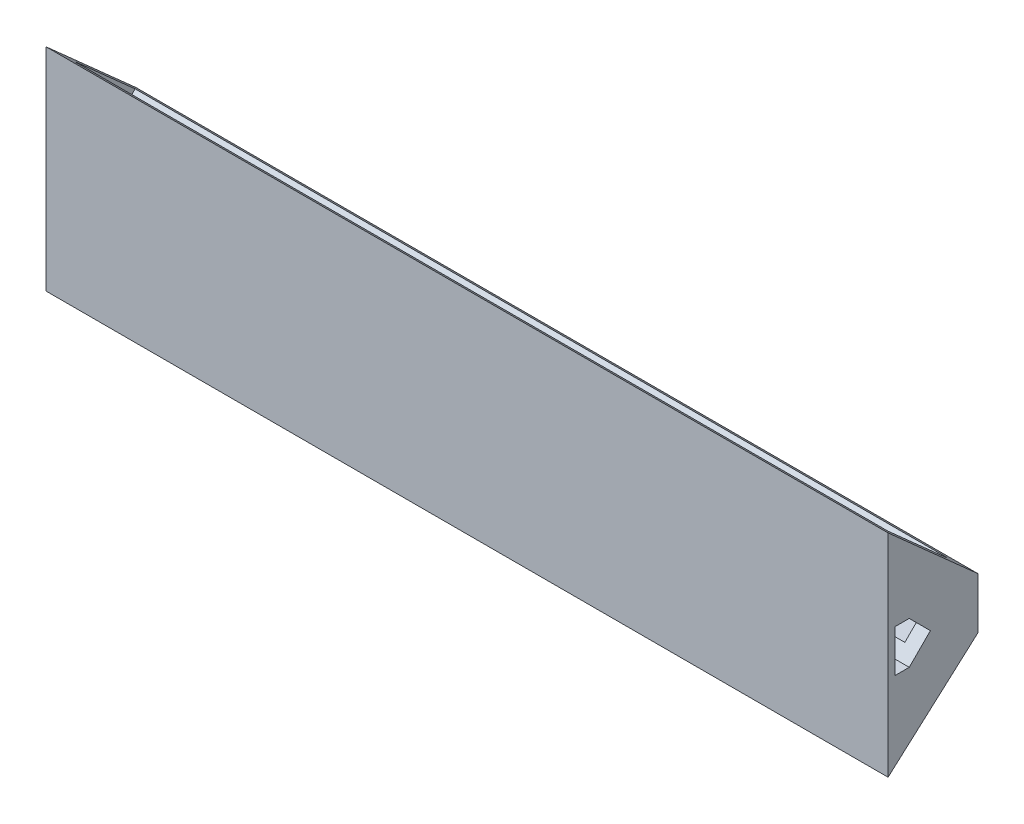
SolidWorks part; units mm, degrees
ref_plane "Front Plane" through (0, 0, 0) normal (0, 0, 1) x (1, 0, 0)
ref_plane "Top Plane" through (0, 0, 0) normal (0, 1, 0) x (1, 0, 0)
ref_plane "Right Plane" through (0, 0, 0) normal (1, 0, 0) x (0, 0, -1)
sketch "Sketch1" plane through (0, 0, 0) normal (0, 0, 1) x (1, 0, 0)
  line L0 (-115.4, 3.25) -> (115.4, -3.25) construction
  line L1 (-115.4, 3.25) -> (115.4, 3.25)
  line L2 (-115.4, 3.25) -> (-115.4, -3.25)
  line L3 (-115.4, -3.25) -> (115.4, -3.25)
  line L4 (115.4, 3.25) -> (115.4, -3.25)
  line L5 (-119.4, 7.25) -> (-119.4, -7.25)
  line L6 (-119.4, -7.25) -> (119.4, -7.25)
  line L7 (119.4, 7.25) -> (119.4, -7.25)
  line L8 (-119.4, 7.25) -> (119.4, 7.25)
  point P9 (0, 0)
  point P10 (0, 0)
  dimension "D1" = 6.5
  dimension "D2" = 230.8
  dimension "D3" = 4
sketch "Sketch4" plane through (0, 0, 0) normal (1, 0, 0) x (0, 0, -1)
  line L0 (-20, 8.7261) -> (-20, -2.0023) construction
  line L1 (0, 7.25) -> (0, -7.25) construction
  line L2 (0, 7.25) -> (-25.5, 30)
  line L3 (-25.5, 30) -> (-25.5, -30)
  line L4 (-25.5, 0) -> (0, 0) construction
  line L5 (-23.5, 6) -> (-23.5, -6)
  line L6 (-23.5, 6) -> (-19.5, 6)
  line L7 (-19.5, 6) -> (-13.5, 0)
  line L8 (-20.5, 4.0321) -> (-20.5, -1.7233) construction
  line L9 (0, -7.25) -> (-25.5, -30)
  line L10 (-19.5, -6) -> (-13.5, 0)
  line L11 (-23.5, -6) -> (-19.5, -6)
  line L12 (0, 7.25) -> (0, -7.25)
  point P9 (0, 0)
  point P12 (-25.5, -30)
  point P13 (-25.5, 30)
  point P14 (0, 5.6555)
  point P15 (0, 0)
  point P22 (-23.5, 0)
  point P23 (0, 0)
  dimension "D1" = 20
  dimension "D2" = 3
  dimension "D3" = 2
  dimension "D4" = 45
  dimension "D5" = 0.5
  dimension "D6" = 6
  dimension "D7" = 4
  dimension "D8" = 30
extrude "Boss-Extrude1" add sketch "Sketch4" along normal up to vertex (119.4 mm away) and the other way up to vertex (119.4 mm away) up to point (119.4, 7.25, 0) other way up to point (-119.4, 7.25, 0)
extrude "Cut-Extrude1" cut sketch "Sketch1" along normal blind 20 contours L1 L4 L3 L2
shell "Shell1" thickness 4 removed face at (0, 18.625, 12.75) removed face at (0, -18.625, 12.75)
chamfer "Chamfer1" distance 4 angle 45 2 edges at (0, -7.25, 4) (0, 7.25, 4)
